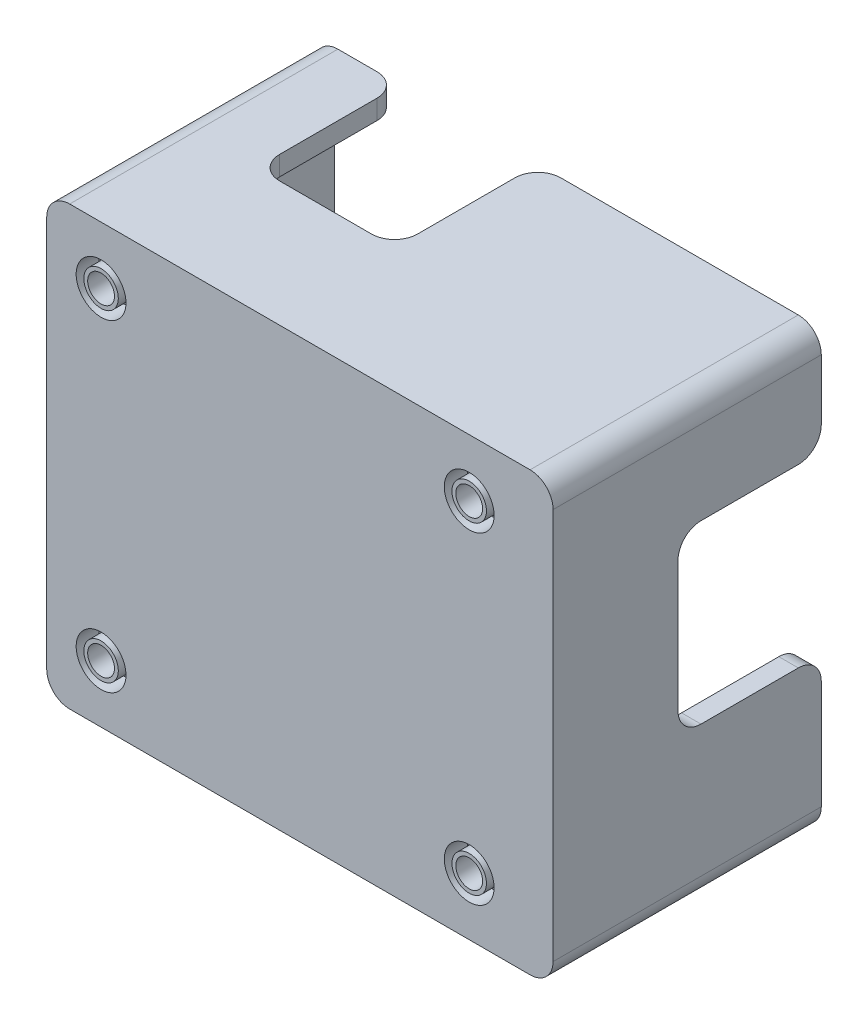
SolidWorks part; units mm, degrees
ref_plane "Front Plane" through (0, 0, 0) normal (0, 0, 1) x (1, 0, 0)
ref_plane "Top Plane" through (0, 0, 0) normal (0, 1, 0) x (1, 0, 0)
ref_plane "Right Plane" through (0, 0, 0) normal (1, 0, 0) x (0, 0, -1)
sketch "Sketch1" plane through (0, 0, 0) normal (0, 0, 1) x (1, 0, 0)
  line L0 (-180.74, 3.9892) -> (-180.74, -3.9892) construction
  line L1 (-211.24, 111.4335) -> (-150.24, 111.4335)
  line L2 (-211.24, 111.4335) -> (-211.24, 59.4335)
  line L3 (-211.24, 59.4335) -> (-150.24, 59.4335)
  line L4 (-150.24, 111.4335) -> (-150.24, 59.4335)
  line L5 (-180.74, 59.4335) -> (-180.74, 111.4335) construction
  line L6 (-211.24, 85.4335) -> (-150.24, 85.4335) construction
  line L7 (6.2759, 85.4335) -> (-6.2759, 85.4335) construction
  line L8 (-209.24, 109.4335) -> (-152.24, 109.4335) construction
  line L9 (-209.24, 61.4335) -> (-209.24, 109.4335) construction
  point P392 (-180.74, 85.4335)
  dimension "D1" = 2
  dimension "D2" = 2
extrude "Boss-Extrude1" add sketch "Sketch1" along normal blind 6
sketch "Sketch2" plane through (0, 0, 6) normal (0, 0, 1) x (1, 0, 0)
  line L4 (-211.24, 111.4335) -> (-211.24, 59.4335)
  line L5 (-211.24, 59.4335) -> (-150.24, 59.4335)
  line L6 (-150.24, 59.4335) -> (-150.24, 111.4335)
  line L7 (-150.24, 111.4335) -> (-211.24, 111.4335)
  line L8 (-211.24, 111.4335) -> (-211.24, 59.4335)
  line L9 (-211.24, 59.4335) -> (-150.24, 59.4335)
  line L10 (-150.24, 59.4335) -> (-150.24, 111.4335)
  line L11 (-150.24, 111.4335) -> (-211.24, 111.4335)
  line L16 (-213.78, 113.9735) -> (-213.78, 56.8935)
  line L17 (-213.78, 56.8935) -> (-147.7, 56.8935)
  line L18 (-147.7, 56.8935) -> (-147.7, 113.9735)
  line L19 (-147.7, 113.9735) -> (-213.78, 113.9735)
  line L20 (-213.78, 113.9735) -> (-213.78, 56.8935)
  line L21 (-213.78, 56.8935) -> (-147.7, 56.8935)
  line L22 (-147.7, 56.8935) -> (-147.7, 113.9735)
  line L23 (-147.7, 113.9735) -> (-213.78, 113.9735)
  dimension "D1" = 0
  dimension "D2" = 2.54
extrude "Boss-Extrude2" add sketch "Sketch2" against normal blind 35
sketch "Sketch3" plane through (0, 0, -29) normal (0, 0, -1) x (-1, 0, 0)
  line L0 (150.24, 111.4335) -> (211.24, 111.4335) construction
  line L1 (202.6875, 111.4335) -> (184.6875, 111.4335)
  line L2 (202.6875, 111.4335) -> (202.6875, 113.9735)
  line L3 (202.6875, 113.9735) -> (184.6875, 113.9735)
  line L4 (184.6875, 111.4335) -> (184.6875, 113.9735)
  line L5 (147.7, 113.9735) -> (213.78, 113.9735) construction
  line L6 (184.6875, 64.3985) -> (184.6875, 106.3985) construction
  line L7 (202.6875, 106.3985) -> (202.6875, 64.3985) construction
  line L8 (150.24, 59.4335) -> (150.24, 111.4335) construction
  line L9 (150.24, 100.0658) -> (147.7, 100.0658)
  line L10 (150.24, 100.0658) -> (150.24, 77.084)
  line L11 (150.24, 77.084) -> (147.7, 77.084)
  line L12 (147.7, 100.0658) -> (147.7, 77.084)
  line L13 (147.7, 56.8935) -> (147.7, 113.9735) construction
  line L14 (147.207, 98.0658) -> (150.8555, 98.0658) construction
  line L15 (151.24, 79.084) -> (158.8923, 79.084) construction
  dimension "D1" = 2
  dimension "D2" = 2
extrude "Cut-Extrude1" cut sketch "Sketch3" against normal offset from surface (18.7 mm away) 1 offset beyond the face yes
fillet "Fillet1" radius 3 16 edges at (-148.97, 77.084, -29) (-148.97, 100.0658, -29) (-184.6875, 112.7035, -29) (-202.6875, 112.7035, -29) (-184.6875, 112.7035, -10.3) (-202.6875, 112.7035, -10.3) (-148.97, 77.084, -10.3) (-148.97, 100.0658, -10.3) (-147.7, 113.9735, -11.5) (-150.24, 111.4335, -14.5) (-150.24, 59.4335, -14.5) (-147.7, 56.8935, -11.5) (-211.24, 59.4335, -14.5) (-213.78, 56.8935, -11.5) (-213.78, 113.9735, -11.5) (-211.24, 111.4335, -14.5)
sketch "Sketch4" plane through (0, 0, 0) normal (0, 0, -1) x (-1, 0, 0)
  circle A26 centre (206.6855, 64.3985) radius 1.75
  circle A27 centre (206.6855, 64.3985) radius 1.75
  circle A29 centre (158.6455, 64.3985) radius 1.75
  circle A30 centre (158.6455, 64.3985) radius 1.75
  circle A36 centre (206.6855, 106.4685) radius 1.75
  circle A37 centre (206.6855, 106.4685) radius 1.75
  circle A43 centre (158.6455, 106.4685) radius 1.75
  circle A44 centre (158.6455, 106.4685) radius 1.75
  dimension "D2" = 0.5
  dimension "D3" = 0.5
  dimension "D4" = 0.5
  dimension "D5" = 0.5
extrude "Cut-Extrude3" cut sketch "Sketch4" against normal through all
sketch "Sketch5" plane through (0, 0, 6) normal (0, 0, 1) x (1, 0, 0)
  circle A6 centre (-206.6855, 64.3985) radius 3.25
  circle A7 centre (-206.6855, 64.3985) radius 3.25
  circle A9 centre (-206.6855, 106.4685) radius 3.25
  circle A10 centre (-206.6855, 106.4685) radius 3.25
  circle A12 centre (-158.6455, 64.3985) radius 3.25
  circle A13 centre (-158.6455, 64.3985) radius 3.25
  circle A15 centre (-158.6455, 106.4685) radius 3.25
  circle A16 centre (-158.6455, 106.4685) radius 3.25
  dimension "D1" = 1.5
  dimension "D2" = 1.5
  dimension "D3" = 1.5
  dimension "D4" = 1.5
extrude "Cut-Extrude4" cut sketch "Sketch5" against normal blind 3
sketch "Sketch6" plane through (0, 0, 6) normal (0, 0, 1) x (1, 0, 0)
  circle A2 centre (-158.6455, 64.3985) radius 2.25
  circle A3 centre (-158.6455, 64.3985) radius 2.25
  circle A10 centre (-206.6855, 106.4685) radius 2.25
  circle A11 centre (-206.6855, 106.4685) radius 2.25
  circle A13 centre (-158.6455, 106.4685) radius 2.25
  circle A14 centre (-158.6455, 106.4685) radius 2.25
  circle A20 centre (-206.6855, 64.3985) radius 1.75 construction
  circle A21 centre (-206.6855, 64.3985) radius 2.25
  circle A22 centre (-206.6855, 64.3985) radius 2.25
  circle A23 centre (-206.6855, 64.3985) radius 1.75
  circle A24 centre (-158.6455, 64.3985) radius 1.75 construction
  circle A25 centre (-158.6455, 106.4685) radius 1.75 construction
  circle A26 centre (-206.6855, 106.4685) radius 1.75 construction
  circle A27 centre (-158.6455, 64.3985) radius 1.75
  circle A28 centre (-158.6455, 106.4685) radius 1.75
  circle A29 centre (-206.6855, 106.4685) radius 1.75
  dimension "D1" = 0.5
  dimension "D2" = 0.5
  dimension "D3" = 0.5
  dimension "D4" = 0.5
extrude "Boss-Extrude3" add sketch "Sketch6" against normal offset from surface (2.75 mm away) 0.25 up to face at (-155.3955, 64.3985, 3)
equation "\"1mmm\"=33.94"
